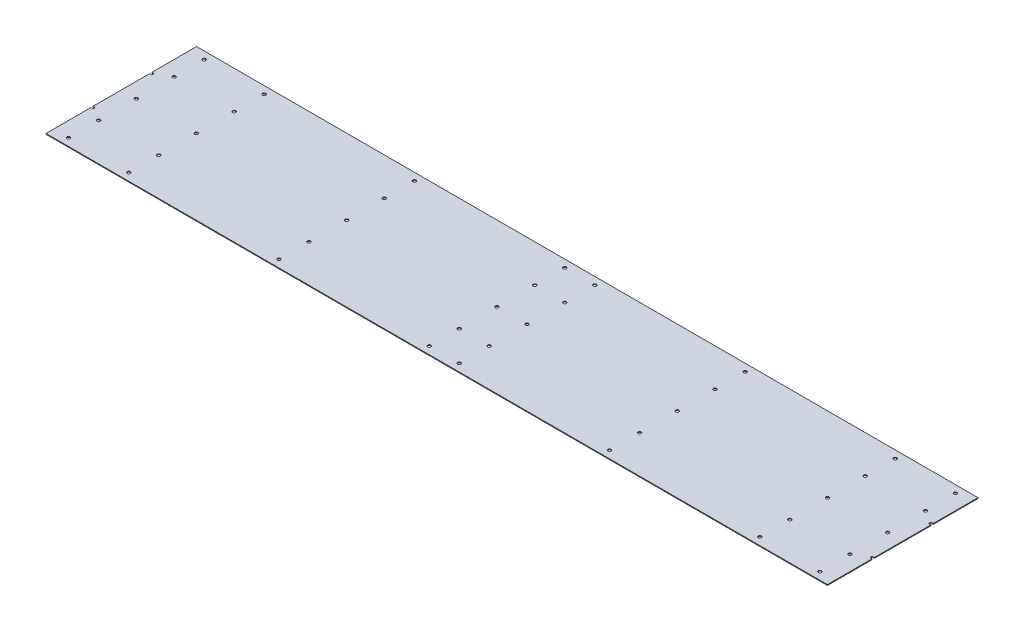
SolidWorks part; units mm, degrees
ref_plane "Front Plane" through (0, 0, 0) normal (0, 0, 1) x (1, 0, 0)
ref_plane "Top Plane" through (0, 0, 0) normal (0, 1, 0) x (1, 0, 0)
ref_plane "Right Plane" through (0, 0, 0) normal (1, 0, 0) x (0, 0, -1)
sketch "Sketch1" plane through (0, 0, 0) normal (0, 1, 0) x (1, 0, 0)
  line L0 (-500, -40.7) -> (-500, -100.2)
  line L1 (-500, -100.2) -> (540, -100.2)
  line L2 (540, -100.2) -> (540, -40.7)
  line L3 (540, -40.7) -> (-500, -40.7) construction
  line L4 (0, 0) -> (-497, 0) construction
  line L5 (-500, -40.7) -> (-497, -40.7)
  line L7 (-497, 40.7) -> (-500, 40.7)
  line L8 (-500, 40.7) -> (-500, 100.2)
  line L9 (-500, 100.2) -> (540, 100.2)
  line L10 (540, 100.2) -> (540, 40.7)
  line L11 (540, 40.7) -> (537, 40.7)
  line L13 (537, -40.7) -> (540, -40.7)
  line L14 (0, 50.2) -> (520, 50.2) construction
  line L15 (-497, 40.7) -> (-497, 37.7)
  line L16 (-497, 40.7) -> (537, 40.7) construction
  line L17 (537, 40.7) -> (537, -40.7) construction
  line L18 (-497, 40.7) -> (-497, -40.7) construction
  line L19 (-497, 37.7) -> (-500, 37.7)
  line L20 (-500, 37.7) -> (-500, -37.7)
  line L21 (-500, -37.7) -> (-497, -37.7)
  line L22 (-497, -37.7) -> (-497, -40.7)
  line L23 (537, 40.7) -> (537, 37.7)
  line L24 (537, 37.7) -> (540, 37.7)
  line L25 (540, 37.7) -> (540, -37.7)
  line L26 (540, -37.7) -> (537, -37.7)
  line L27 (537, -37.7) -> (537, -40.7)
  line L28 (540, 0) -> (537, 0) construction
  line L29 (520, 50.2) -> (520, -50.2) construction
  line L30 (-497, 0) -> (-500, 0) construction
  line L31 (0, 50.2) -> (0, -50.2) construction
  line L32 (520, -50.2) -> (0, -50.2) construction
  line L33 (0, 50.2) -> (0, 90.2) construction
  line L34 (0, 90.2) -> (520, 90.2) construction
  line L35 (520, 90.2) -> (520, 50.2) construction
  line L36 (520, -50.2) -> (520, -90.2) construction
  line L37 (520, -90.2) -> (0, -90.2) construction
  line L38 (0, -90.2) -> (0, -50.2) construction
  line L39 (0, 0) -> (520, 0) construction
  line L40 (-200, 90.2) -> (-200, 50.2) construction
  line L41 (-200, 50.2) -> (-200, 0) construction
  line L42 (-200, 0) -> (-200, -50.2) construction
  line L43 (-200, -50.2) -> (-200, -90.2) construction
  line L44 (40, 90.2) -> (40, -90.2) construction
  line L45 (-400, 90.2) -> (-480, 90.2) construction
  line L46 (-480, 90.2) -> (-480, -90.2) construction
  line L47 (-480, -90.2) -> (-400, -90.2) construction
  line L48 (-400, -90.2) -> (-400, 90.2) construction
  line L49 (-400, 90.2) -> (0, 90.2) construction
  line L50 (440, 90.2) -> (440, -90.2) construction
  line L51 (-400, 50.2) -> (0, 50.2) construction
  line L52 (440, -90.2) -> (520, -90.2) construction
  line L53 (-400, -50.2) -> (0, -50.2) construction
  line L55 (-480, -90.2) -> (0, -90.2) construction
  line L56 (440, -50.2) -> (520, -50.2) construction
  line L58 (440, 0) -> (520, 0) construction
  line L60 (440, 50.2) -> (520, 50.2) construction
  line L62 (440, 90.2) -> (520, 90.2) construction
  circle A0 centre (0, -50.2) radius 2.15
  circle A30 centre (0, 50.2) radius 2.15
  circle A31 centre (0, -90.2) radius 2.15
  circle A32 centre (0, 90.2) radius 2.15
  circle A33 centre (-200, -90.2) radius 2.15
  circle A34 centre (-200, -50.2) radius 2.15
  circle A35 centre (-200, 50.2) radius 2.15
  circle A36 centre (-200, 90.2) radius 2.15
  circle A53 centre (0, 0) radius 2.15
  circle A55 centre (-200, 0) radius 2.15
  circle A56 centre (-400, 0) radius 2.15
  circle A57 centre (-400, -90.2) radius 2.15
  circle A58 centre (-400, -50.2) radius 2.15
  circle A59 centre (-400, 50.2) radius 2.15
  circle A60 centre (-400, 90.2) radius 2.15
  circle A61 centre (40, -90.2) radius 2.15
  circle A62 centre (40, -50.2) radius 2.15
  circle A63 centre (40, 0) radius 2.15
  circle A64 centre (40, 50.2) radius 2.15
  circle A65 centre (40, 90.2) radius 2.15
  circle A66 centre (520, 90.2) radius 2.15
  circle A67 centre (520, 50.2) radius 2.15
  circle A68 centre (520, 0) radius 2.15
  circle A69 centre (520, -50.2) radius 2.15
  circle A70 centre (520, -90.2) radius 2.15
  circle A71 centre (240, -90.2) radius 2.15
  circle A72 centre (240, -50.2) radius 2.15
  circle A73 centre (240, 0) radius 2.15
  circle A74 centre (240, 50.2) radius 2.15
  circle A75 centre (240, 90.2) radius 2.15
  circle A76 centre (440, -90.2) radius 2.15
  circle A77 centre (440, -50.2) radius 2.15
  circle A78 centre (440, 0) radius 2.15
  circle A79 centre (440, 50.2) radius 2.15
  circle A80 centre (440, 90.2) radius 2.15
  circle A81 centre (-480, 90.2) radius 2.15
  circle A82 centre (-480, 50.2) radius 2.15
  circle A83 centre (-480, 0) radius 2.15
  circle A84 centre (-480, -90.2) radius 2.15
  circle A85 centre (-480, -50.2) radius 2.15
  dimension "D12" = 4.3
  dimension "D13" = 12.5
  dimension "D11" = 200
  dimension "D2" = 75.4
  dimension "D3" = 3
  dimension "D6" = 10
  dimension "D7" = 40
  dimension "D16" = 12.5
  dimension "D8" = 3
  dimension "D4" = 40
  dimension "D17" = 200
  dimension "D5" = 80
  dimension "D15" = 20
  dimension "D18" = 80
  dimension "D19" = 20
  dimension "D20" = 1040
  dimension "D9" = 3
  dimension "D14" = 3
  dimension "D10" = 3
extrude "Boss-Extrude1" add sketch "Sketch1" along normal blind 1 contours L27 L26 L25 L24 L23 L11 L10 L9 L8 L7 L15 L19 L20 L21 L22 L5 L0 L1 L2 L13 A59 A60 A58 A74 A53 A36 A35 A34 A33 A32 A31 A30 A0 region at (20, 0, 0)
equation "\"skin_sheetmetal_thickness\"= 0.80"
equation "\"base_width_skin_spacer\" = \"base_width_skin_target_width\" - 4 * \"skin_sheetmetal_thickness\" - 2 * \"base_width_skin_target_bend_radius\""
equation "\"base_width_skin_inner\" = \"base_width_skin_spacer\" + 2 * \"skin_sheetmetal_thickness\""
equation "\"base_width_skin_outer\" = \"base_width_skin_inner\" + 2 * \"skin_sheetmetal_thickness\""
equation "\"bend_cut_width\"= 3"
equation "\"bend_cut_length\"= 3"
equation "\"bend_offset_inner\"= 12.5"
equation "\"bend_offset_outer\" = \"bend_offset_inner\" + \"skin_sheetmetal_thickness\""
equation "\"border_offset_ends\"= 20"
equation "\"border_offset_sides\"= 10"
equation "\"border_offset_flange_horiz\"= 10"
equation "\"rivet_size\"= 4.3"
equation "\"rivet_offset_ends\"= \"rivet_spacing_horiz\"/2 - \"border_offset_ends\""
equation "\"rivet_spacing_horiz\"= 200"
equation "\"rivet_spacing_vert\"= 40"
equation "\"rivet_spacing_offset_right\"= 40"
equation "\"base_length\"= 200"
equation "\"base_width_skin_spacer_length\" = 430"
equation "\"bend_offset_spacer_tab\"= 21.0"
equation "\"D2@Sketch1\"=\"base_width_skin_inner\""
equation "\"D3@Sketch1\"=\"bend_cut_length\""
equation "\"D8@Sketch1\"=\"bend_cut_width\""
equation "\"D16@Sketch1\"=\"bend_offset_inner\""
equation "\"D7@Sketch1\"=\"rivet_spacing_vert\""
equation "\"D12@Sketch1\"=\"rivet_size\""
equation "\"D6@Sketch1\"=\"border_offset_flange_horiz\""
equation "\"D11@Sketch1\"=\"rivet_spacing_horiz\""
equation "\"D4@Sketch1\"=\"rivet_spacing_offset_right\""
equation "\"D17@Sketch1\"=\"rivet_spacing_horiz\""
equation "\"D5@Sketch1\"=\"rivet_offset_ends\""
equation "\"D15@Sketch1\"=\"border_offset_ends\""
equation "\"D18@Sketch1\"=\"rivet_offset_ends\""
equation "\"D19@Sketch1\"=\"border_offset_ends\""
equation "\"base_width_skin_target_width\" = 80"
equation "\"base_width_skin_target_bend_radius\" = 1.5"
